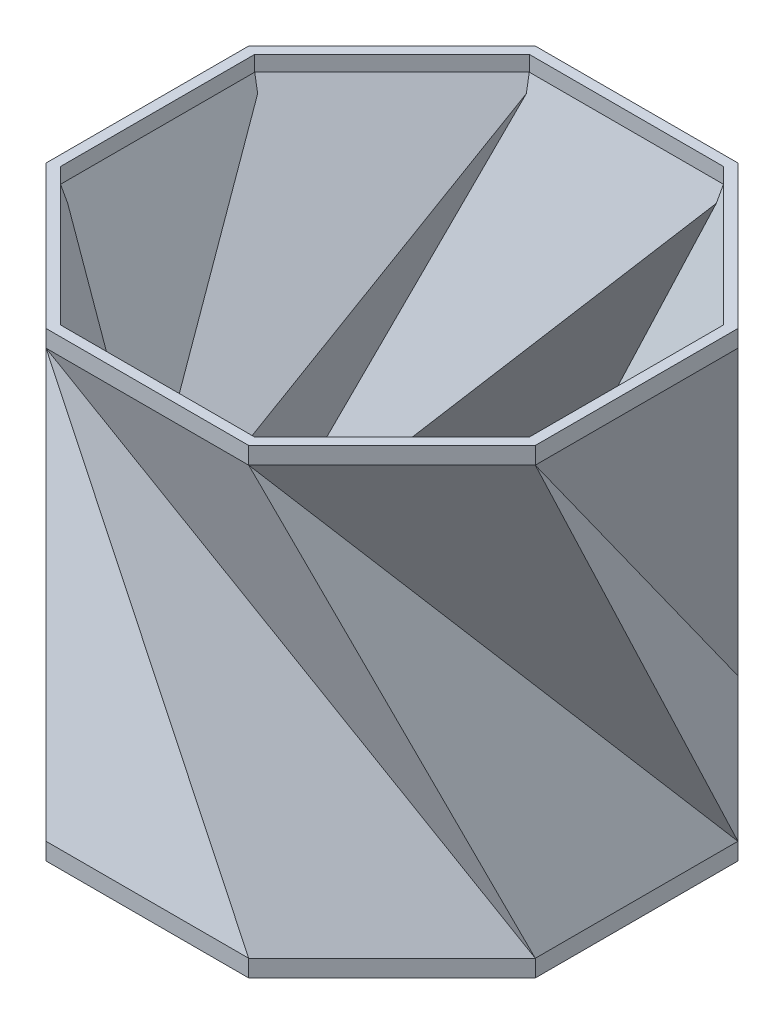
SolidWorks part; units mm, degrees
ref_plane "정면" through (0, 0, 0) normal (0, 0, 1) x (1, 0, 0)
ref_plane "윗면" through (0, 0, 0) normal (0, 1, 0) x (1, 0, 0)
ref_plane "우측면" through (0, 0, 0) normal (1, 0, 0) x (0, 0, -1)
sketch "스케치1" plane through (0, 0, 0) normal (0, 1, 0) x (1, 0, 0)
  line L0 (-55, 0) -> (55, 0) construction
  line L1 (5.9316, -14.3201) -> (14.3201, -5.9316)
  line L2 (14.3201, -5.9316) -> (14.3201, 5.9316)
  line L3 (14.3201, 5.9316) -> (5.9316, 14.3201)
  line L4 (5.9316, 14.3201) -> (-5.9316, 14.3201)
  line L5 (-5.9316, 14.3201) -> (-14.3201, 5.9316)
  line L6 (-14.3201, 5.9316) -> (-14.3201, -5.9316)
  line L7 (-14.3201, -5.9316) -> (-5.9316, -14.3201)
  line L8 (-5.9316, -14.3201) -> (5.9316, -14.3201)
  circle A0 centre (0, 0) radius 14.3201 construction
  dimension "D1" = 31
extrude "보스-돌출1" add sketch "스케치1" along normal blind 25
sketch "스케치9" plane through (0, 25, 0) normal (0, 1, 0) x (1, 0, 0)
  line L8 (-5.9316, -14.3201) -> (5.9316, -14.3201)
  line L9 (5.9316, -14.3201) -> (14.3201, -5.9316)
  line L13 (-5.9316, -14.3201) -> (5.9316, -14.3201)
  line L25 (14.3201, -5.9316) -> (14.3201, 5.9316)
  line L29 (14.3201, -5.9316) -> (14.3201, 5.9316)
  line L32 (14.3201, 5.9316) -> (5.9316, 14.3201)
  line L34 (14.3201, 5.9316) -> (5.9316, 14.3201)
  line L36 (5.9316, 14.3201) -> (-5.9316, 14.3201)
  line L38 (5.9316, 14.3201) -> (-5.9316, 14.3201)
  line L39 (-5.9316, 14.3201) -> (-14.3201, 5.9316)
  line L40 (-5.9316, 14.3201) -> (-14.3201, 5.9316)
  line L41 (-14.3201, 5.9316) -> (-14.3201, -5.9316)
  line L42 (-14.3201, 5.9316) -> (-14.3201, -5.9316)
  line L43 (-14.3201, -5.9316) -> (-5.9316, -14.3201)
  line L44 (-14.3201, -5.9316) -> (-5.9316, -14.3201)
  line L45 (5.9316, -14.3201) -> (14.3201, -5.9316)
  dimension "D1" = 0
sketch "스케치10" plane through (0, 0, 0) normal (0, -1, 0) x (1, 0, 0)
  line L8 (5.9316, 14.3201) -> (-5.9316, 14.3201)
  line L9 (-5.9316, 14.3201) -> (-14.3201, 5.9316)
  line L13 (-5.9316, 14.3201) -> (-14.3201, 5.9316)
  line L25 (-14.3201, 5.9316) -> (-14.3201, -5.9316)
  line L29 (-14.3201, 5.9316) -> (-14.3201, -5.9316)
  line L32 (-14.3201, -5.9316) -> (-5.9316, -14.3201)
  line L34 (-14.3201, -5.9316) -> (-5.9316, -14.3201)
  line L36 (-5.9316, -14.3201) -> (5.9316, -14.3201)
  line L38 (-5.9316, -14.3201) -> (5.9316, -14.3201)
  line L39 (5.9316, -14.3201) -> (14.3201, -5.9316)
  line L40 (5.9316, -14.3201) -> (14.3201, -5.9316)
  line L41 (14.3201, -5.9316) -> (14.3201, 5.9316)
  line L42 (14.3201, -5.9316) -> (14.3201, 5.9316)
  line L43 (14.3201, 5.9316) -> (5.9316, 14.3201)
  line L44 (14.3201, 5.9316) -> (5.9316, 14.3201)
  line L45 (5.9316, 14.3201) -> (-5.9316, 14.3201)
  dimension "D1" = 0
ref_plane "평면2" through (9.1012, 4.3188, -9.1012) normal (-0.6704, -0.3181, 0.6704) x (0.7416, -0.2561, 0.6201)
sketch "스케치12" plane through (9.1012, 4.3188, -9.1012) normal (-0.6704, -0.3181, 0.6704) x (0.7416, -0.2561, 0.6201)
  line L0 (7.8961, 24.8714) -> (6.9415, -2.7841)
  line L1 (7.8961, 24.8714) -> (-4.4808, -5.9881)
sketch "스케치13" plane through (10.1259, 0, -10.1259) normal (0.7071, 0, -0.7071) x (-0.7071, 0, -0.7071)
  line L0 (-5.9316, 25) -> (5.9316, 0)
ref_plane "평면3" through (5.9316, 0, -14.3201) normal (-0.2523, -0.7519, -0.6091) x (-0.9675, 0.2052, 0.1474)
sketch "스케치14" plane through (5.9316, 0, -14.3201) normal (-0.2523, -0.7519, -0.6091) x (-0.9675, 0.2052, 0.1474)
  line L0 (0, 0) -> (-6.8796, -6.4183) construction
  line L1 (-1.7489, 9.2447) -> (0, 0) construction
  line L2 (0, 0) -> (-6.8796, -6.4183)
  line L3 (-1.7489, 9.2447) -> (0, 0)
  line L4 (-6.8796, -6.4183) -> (-1.7489, 9.2447)
extrude "컷-돌출1" cut sketch "스케치14" against normal up to vertex (33.2491 mm away) up to point (14.3201, 25, 5.9316)
pattern_circular "원형 패턴1" count 8 over 360 about axis through (0, 25, 0) along (0, 1, 0) of "컷-돌출1"
extrude "보스-돌출2" add sketch "스케치9" along normal blind 1
extrude "보스-돌출3" add sketch "스케치10" along normal blind 1
shell "쉘1" thickness 0.6 removed face at (0, -1, 0) removed face at (0, 26, 0)
